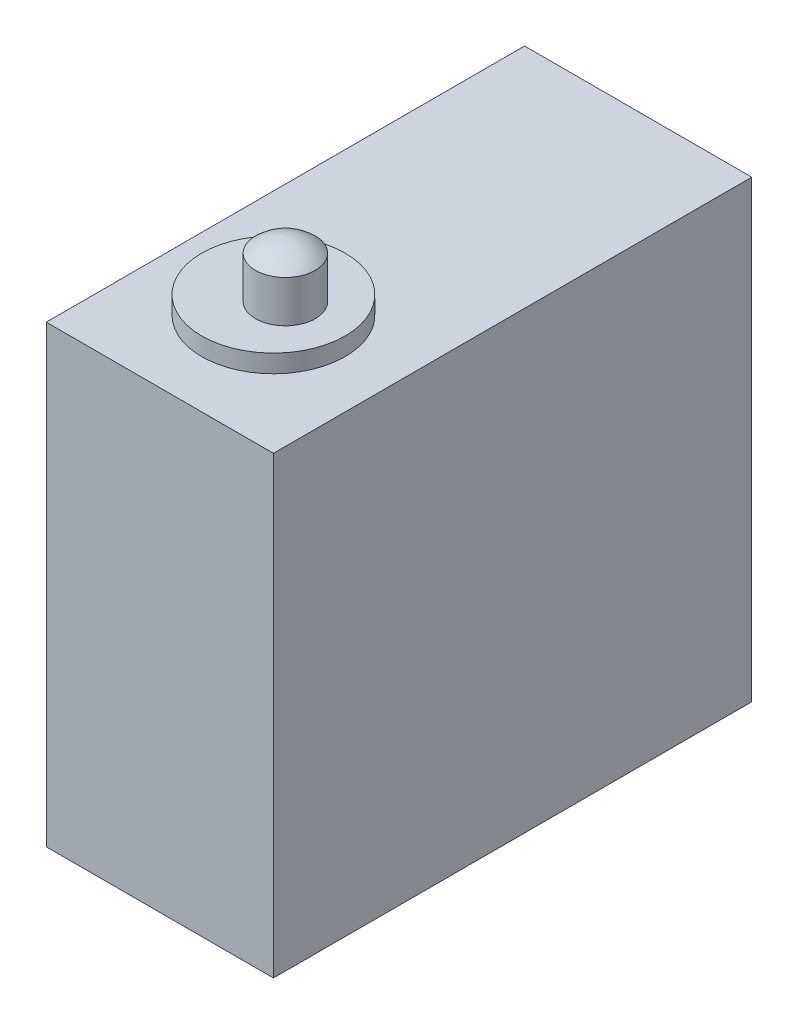
SolidWorks part; units mm, degrees
ref_plane "Plan de face" through (0, 0, 0) normal (0, 0, 1) x (1, 0, 0)
ref_plane "Plan de dessus" through (0, 0, 0) normal (0, 1, 0) x (1, 0, 0)
ref_plane "Plan de droite" through (0, 0, 0) normal (1, 0, 0) x (0, 0, -1)
sketch "Esquisse1" plane through (0, 0, 0) normal (1, 0, 0) x (0, 0, -1)
  line L1 (15.1663, 17.3368) -> (-24.8337, 17.3368)
  line L2 (15.1663, 17.3368) -> (15.1663, -20.6632)
  line L3 (15.1663, -20.6632) -> (-24.8337, -20.6632)
  line L4 (-24.8337, 17.3368) -> (-24.8337, -20.6632)
  dimension "D1" = 40
  dimension "D2" = 38
extrude "Extrusion1" add sketch "Esquisse1" along normal blind 19
sketch "Esquisse2" plane through (0, 17.3368, 0) normal (0, 1, 0) x (1, 0, 0)
  line L0 (19, 15.1663) -> (19, -24.8337) construction
  line L1 (1.7125, -4.8337) -> (18.3582, -4.8337) construction
  line L2 (19, 15.1663) -> (0, 15.1663) construction
  circle A0 centre (9, -14.8337) radius 6
  dimension "D1" = 10
  dimension "D2" = 20
  dimension "D3" = 10
extrude "Extrusion2" add sketch "Esquisse2" along normal blind 1.5
sketch "Esquisse3" plane through (0, 18.8368, 0) normal (0, 1, 0) x (-1, 0, 0)
  line L0 (0, -15.1663) -> (0, 24.8337) construction
  line L1 (-19, 24.8337) -> (0, 24.8337) construction
  circle A0 centre (-10, 14.8337) radius 2.5
  dimension "D1" = 10
  dimension "D2" = 10
extrude "Extrusion3" add sketch "Esquisse3" along normal blind 3.5
dome "Dôme1" faces to dome 1 distance 1 reverse direction no elliptical dome no face at (10, 22.3368, 17.3337) parameters "D1"=1
